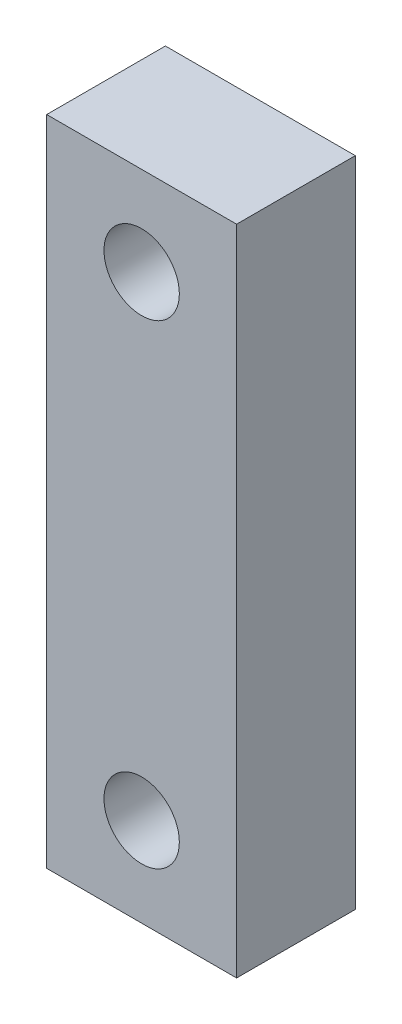
SolidWorks part; units mm, degrees
ref_plane "Front Plane" through (0, 0, 0) normal (0, 0, 1) x (1, 0, 0)
ref_plane "Top Plane" through (0, 0, 0) normal (0, 1, 0) x (1, 0, 0)
ref_plane "Right Plane" through (0, 0, 0) normal (1, 0, 0) x (0, 0, -1)
sketch "Sketch1" plane through (0, 0, 0) normal (0, 0, 1) x (1, 0, 0)
  line L0 (0, 0) -> (0, 40) construction
  line L2 (8, -7.5) -> (-8, -7.5)
  line L3 (8, -7.5) -> (8, 47.5)
  line L4 (8, 47.5) -> (-8, 47.5)
  line L5 (-8, -7.5) -> (-8, 47.5)
  line L6 (8, -7.5) -> (-8, 47.5) construction
  line L7 (8, 47.5) -> (-8, -7.5) construction
  circle A0 centre (0, 40) radius 3.175
  circle A1 centre (0, 0) radius 3.175
  point P5 (0, 20)
  dimension "D2" = 6.35
  dimension "D1" = 40
  dimension "D3" = 55
  dimension "D4" = 16
extrude "Boss-Extrude1" add sketch "Sketch1" along normal blind 10
